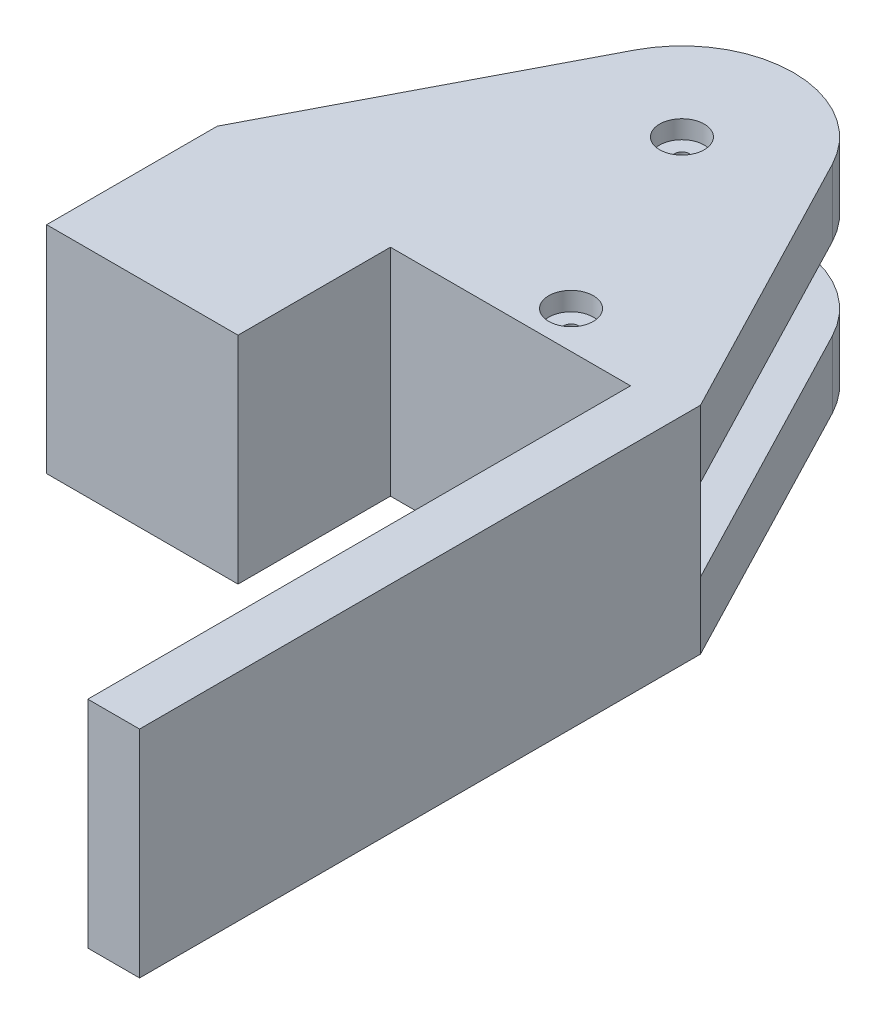
SolidWorks part; units mm, degrees
material "Copper"
ref_plane "Front Plane" through (0, 0, 0) normal (0, 0, 1) x (1, 0, 0)
ref_plane "Top Plane" through (0, 0, 0) normal (0, 1, 0) x (1, 0, 0)
ref_plane "Right Plane" through (0, 0, 0) normal (1, 0, 0) x (0, 0, -1)
sketch "Sketch1" plane through (0, 0, 0) normal (0, 0, 1) x (1, 0, 0)
  line L0 (0, 11) -> (65, 11)
  line L1 (0, 0) -> (65, 0)
  line L2 (0, 0) -> (0, 65)
  line L3 (0, 65) -> (65, 65)
  line L4 (65, 0) -> (65, 65)
  line L5 (0, 0) -> (65, 0)
  line L6 (0, 0) -> (0, 10)
  line L7 (0, 10) -> (65, 10)
  line L8 (65, 0) -> (65, 10)
  line L9 (0, 10) -> (65, 10)
  line L10 (0, 10) -> (0, 20)
  line L11 (0, 20) -> (65, 20)
  line L12 (65, 10) -> (65, 20)
  line L13 (65, 20) -> (0, 20)
  line L14 (65, 20) -> (65, 30)
  line L15 (65, 30) -> (0, 30)
  line L16 (0, 20) -> (0, 30)
  line L17 (0, 30) -> (65, 30)
  line L18 (0, 30) -> (0, 40)
  line L19 (0, 40) -> (65, 40)
  line L20 (65, 30) -> (65, 40)
  line L21 (0, 31) -> (65, 31)
  line L22 (36.97, 30) -> (36.97, 31) construction
  line L23 (37.8533, 10) -> (37.8533, 11) construction
  dimension "D1" = 65
  dimension "D2" = 65
  dimension "D3" = 10
  dimension "D4" = 1
extrude "Boss-Extrude1" add sketch "Sketch1" along normal blind 45 contours L11 L2 L7 L4 | L19 L2 L15 L4 region at (32.5, 15.5, 0) region at (32.5, 35.5, 0)
sketch "Sketch2" plane through (0, 10, 0) normal (0, -1, 0) x (1, 0, 0)
  line L0 (32.5, 0) -> (32.5, 45) construction
  line L3 (0, 45) -> (19.1907, 8.0816)
  line L4 (65, 45) -> (45.8093, 8.0816)
  line L5 (0, 45) -> (0, 0)
  line L6 (0, 0) -> (65, 0)
  line L7 (65, 0) -> (65, 45)
  circle A0 centre (32.5, 15) radius 15
  circle A1 centre (32.5, 15) radius 1
  dimension "D1" = 30
  dimension "D2" = 2
extrude "Cut-Extrude5" cut sketch "Sketch2" against normal blind 34 contours A0 L6 L4 | L0 A1 | A1 L0 | A1 region at (56.7767, 10, 14.6593) region at (32.0756, 10, 15) region at (32.9244, 10, 15)
extrude "Cut-Extrude6" cut sketch "Sketch2<6>" against normal blind 34 contours A0 L3 region at (8.2233, 10, 14.6593)
sketch "Sketch2<6>" plane through (0, 10, 0) normal (0, -1, 0) x (1, 0, 0) same geometry as "Sketch2"
sketch "Sketch3" plane through (0, 40, 0) normal (0, 1, 0) x (1, 0, 0)
  circle A0 centre (32.5, -15) radius 3
  dimension "D1" = 6
extrude "Cut-Extrude7" cut sketch "Sketch3" against normal blind 2.45
sketch "Sketch4" plane through (0, 20, 0) normal (0, 1, 0) x (1, 0, 0)
  circle A0 centre (32.5, -15) radius 3
extrude "Cut-Extrude8" cut sketch "Sketch4" against normal blind 2.45
sketch "Sketch5" plane through (0, 0, 45) normal (0, 0, 1) x (1, 0, 0)
  line L1 (0, 11) -> (65, 11)
  line L2 (0, 11) -> (0, 40)
  line L3 (0, 40) -> (65, 40)
  line L4 (65, 11) -> (65, 40)
extrude "Boss-Extrude2" add sketch "Sketch5" along normal blind 2.45
sketch "Sketch9" plane through (0, 0, 47.45) normal (0, 0, 1) x (1, 0, 0)
  line L0 (65, 40) -> (0, 40) construction
  line L1 (65, 11) -> (58.0376, 11)
  line L2 (65, 11) -> (65, 40)
  line L3 (65, 40) -> (58.0376, 40)
  line L4 (58.0376, 11) -> (58.0376, 40)
extrude "Boss-Extrude5" add sketch "Sketch9" along normal blind 73
sketch "Sketch13" plane through (0, 0, 47.45) normal (0, 0, 1) x (1, 0, 0)
  line L0 (0, 11) -> (58.0376, 11) construction
  line L1 (25.7437, 11) -> (0, 11)
  line L2 (25.7437, 11) -> (25.7437, 40)
  line L3 (25.7437, 40) -> (0, 40)
  line L4 (0, 11) -> (0, 40)
extrude "Boss-Extrude6" add sketch "Sketch13" along normal blind 20.5
sketch "Sketch11" plane through (0, 40, 0) normal (0, 1, 0) x (1, 0, 0)
  line L0 (45.0376, -42.45) -> (45.0376, -47.45) construction
  line L1 (58.0376, -47.45) -> (25.7437, -47.45) construction
  line L2 (58.0376, -120.45) -> (58.0376, -47.45) construction
  circle A0 centre (45.0376, -42.45) radius 3
  dimension "D1" = 6
  dimension "D2" = 5
  dimension "D3" = 13
extrude "Cut-Extrude11" cut sketch "Sketch11" against normal blind 2.5
sketch "Sketch12" plane through (0, 37.5, 0) normal (0, 1, 0) x (1, 0, 0)
  circle A0 centre (45.0376, -42.45) radius 1
extrude "Cut-Extrude12" cut sketch "Sketch12" against normal blind 32.5
